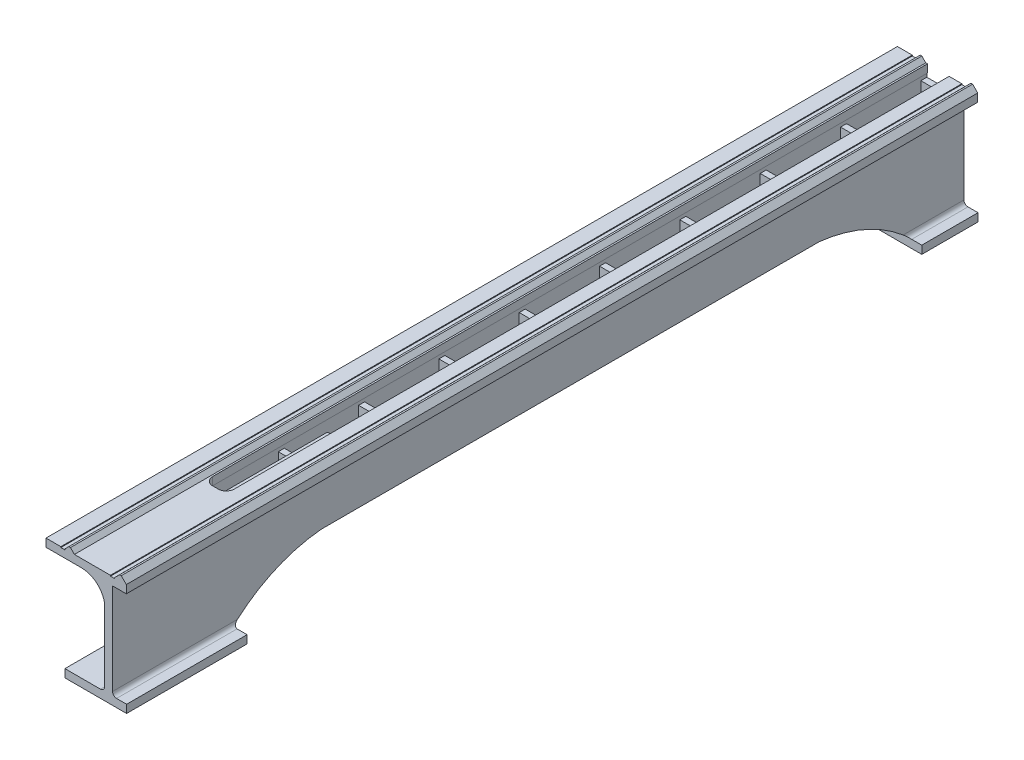
SolidWorks part; units mm, degrees
ref_plane "Front Plane" through (0, 0, 0) normal (0, 0, 1) x (1, 0, 0)
ref_plane "Top Plane" through (0, 0, 0) normal (0, 1, 0) x (1, 0, 0)
ref_plane "Right Plane" through (0, 0, 0) normal (1, 0, 0) x (0, 0, -1)
sketch "Sketch1" plane through (0, 0, 0) normal (0, 0, 1) x (1, 0, 0)
  line L0 (-31.5551, 31.2902) -> (-37.8538, 37.7187)
  line L2 (-131.555, 31.42) -> (-131.555, 21.42)
  line L4 (-31.5551, 31.2902) -> (-31.5551, 21.2902)
  line L5 (-37.8538, 37.7187) -> (-39.8538, 37.7187)
  line L6 (-39.8538, 37.7187) -> (-46.2824, 31.42)
  line L7 (-46.2824, 31.42) -> (-46.2824, 30.42)
  line L8 (-46.2824, 30.42) -> (-51.2824, 30.42)
  line L9 (-51.2824, 30.42) -> (-51.2824, 31.42)
  line L10 (-51.2824, 31.42) -> (-96.2063, 31.42)
  line L14 (-96.2063, 31.42) -> (-101.1053, 36.42)
  line L15 (-101.1053, 36.42) -> (-103.1053, 36.42)
  line L16 (-103.1053, 36.42) -> (-108.055, 31.4703)
  line L17 (-108.055, 31.4703) -> (-108.055, 30.42)
  line L18 (-108.055, 30.42) -> (-113.055, 30.42)
  line L19 (-113.055, 30.42) -> (-113.055, 31.42)
  line L20 (-113.055, 31.42) -> (-131.555, 31.42)
  line L21 (-131.555, 21.42) -> (-87.3496, 21.42)
  line L22 (-31.5551, 21.2902) -> (-48.7011, 21.2902)
  line L23 (-48.7011, 21.2902) -> (-48.7011, -92.58)
  line L24 (-43.7011, -97.58) -> (-31.1954, -97.58)
  line L25 (-31.1954, -97.58) -> (-31.1954, -107.58)
  line L26 (-31.1954, -107.58) -> (-108.01, -107.58)
  line L27 (-108.01, -107.58) -> (-108.01, -97.58)
  line L28 (-108.01, -97.58) -> (-63.7011, -97.58)
  line L29 (-58.7011, -92.58) -> (-58.7011, -1.9527)
  arc A0 (-87.3496, 21.42) -> (-58.7011, -1.9527) centre (-87.3496, -7.8239) cw
  arc A1 (-48.7011, -92.58) -> (-43.7011, -97.58) centre (-43.7011, -92.58) ccw
  arc A2 (-63.7011, -97.58) -> (-58.7011, -92.58) centre (-63.7011, -92.58) ccw
  point P30 (-48.7011, -97.58)
  dimension "D17" = 5
  dimension "D1" = 100
  dimension "D2" = 7
  dimension "D3" = 2
  dimension "D4" = 5
  dimension "D5" = 18.5
  dimension "D6" = 5
  dimension "D7" = 10
  dimension "D8" = 135
  dimension "D9" = 9
  dimension "D10" = 9
  dimension "D11" = 2
  dimension "D12" = 7
  dimension "D13" = 10
  dimension "D14" = 5
  dimension "D15" = 10
  dimension "D16" = 139
  dimension "D18" = 10
  dimension "D19" = 1
extrude "Boss-Extrude1" add sketch "Sketch1" along normal blind 1060
sketch "Sketch2" plane through (0, 20.7647, 0) normal (0, 1, 0) x (1, 0, 0)
  line L0 (-94.1707, -1200) -> (-94.1707, 0) construction
  line L1 (-84.1707, 100) -> (-77.1707, 100)
  line L2 (-94.1707, 90) -> (-94.1707, -890)
  line L3 (-84.1707, -900) -> (-77.1707, -900)
  line L4 (-67.1707, 90) -> (-67.1707, -890)
  line L5 (-67.1707, -1200) -> (-67.1707, 0) construction
  line L6 (-51.2824, 0) -> (-96.2063, 0) construction
  arc A0 (-94.1707, -890) -> (-84.1707, -900) centre (-84.1707, -890) ccw
  arc A1 (-77.1707, -900) -> (-67.1707, -890) centre (-77.1707, -890) ccw
  arc A2 (-77.1707, 100) -> (-67.1707, 90) centre (-77.1707, 90) cw
  arc A3 (-84.1707, 100) -> (-94.1707, 90) centre (-84.1707, 90) ccw
  point P12 (-67.1707, -900)
  point P15 (-67.1707, 100)
  point P18 (-94.1707, 100)
  dimension "D2" = 10
  dimension "D1" = 1000
  dimension "D3" = 100
extrude "Cut-Extrude1" cut sketch "Sketch2" along normal blind 800
sketch "Sketch3" plane through (0, 0, 1060) normal (0, 0, 1) x (1, 0, 0)
  line L1 (-57.7636, 8.0977) -> (-93.9675, 8.0977)
  line L2 (-57.7636, 8.0977) -> (-57.7636, 21.2819)
  line L3 (-57.7636, 21.2819) -> (-93.9675, 21.2819)
  line L4 (-93.9675, 8.0977) -> (-93.9675, 21.2819)
extrude "Cut-Extrude2" cut sketch "Sketch3" against normal blind 900 from offset 300 offset against normal yes
sketch "Sketch5" plane through (0, 0, 0) normal (0, 0, -1) x (-1, 0, 0)
  line L1 (105.3464, -97.4955) -> (94.9198, -97.4955)
  line L2 (105.3464, -97.4955) -> (105.3464, 27.7967)
  line L3 (105.3464, 27.7967) -> (94.9198, 27.7967)
  line L4 (94.9198, -97.4955) -> (94.9198, 27.7967)
extrude "Boss-Extrude2" add sketch "Sketch5" against normal blind 950
sketch "Sketch6" plane through (-105.3464, 0, 0) normal (-1, 0, 0) x (0, 0, 1)
  line L0 (0, -97.4955) -> (0, 21.42) construction
  line L1 (0, 16.5847) -> (7.4351, 16.5847)
  line L2 (0, 16.5847) -> (0, -47.4448)
  line L3 (0, -47.4448) -> (7.4351, -47.4448)
  line L4 (7.4351, 16.5847) -> (7.4351, -47.4448)
extrude "Boss-Extrude3" add sketch "Sketch6" against normal blind 50
pattern_linear "LPattern1" count 10 spacing 100 along (0, 0, 1) of "Boss-Extrude3"
sketch "Sketch4" plane through (-31.5551, 0, 0) normal (1, 0, 0) x (0, 0, -1)
  line L0 (-910, -97.58) -> (-910, -107.58)
  line L1 (-1060, -97.58) -> (0, -97.58) construction
  line L2 (-1060, -107.58) -> (0, -107.58) construction
  line L3 (-910, -107.58) -> (-910, -177.9566)
  line L4 (-910, -177.9566) -> (-70, -177.9566)
  line L5 (-70, -177.9566) -> (-70, -97.58)
  line L6 (-800, -47.58) -> (-180.0688, -47.58)
  line L7 (0, -92.58) -> (0, 21.2902) construction
  line L8 (-1060, -92.58) -> (-1060, 21.2902) construction
  arc A1 (-800, -47.58) -> (-910, -97.58) centre (-783.4011, -230.0975) ccw
  arc A2 (-180.0688, -47.58) -> (-70, -97.58) centre (-201.6096, -241.1508) cw
  point P17 (-795.844, -47.58)
  dimension "D1" = 60
  dimension "D2" = 70
  dimension "D3" = 150
  dimension "D4" = 110
  dimension "D5" = 110.0688
extrude "Cut-Extrude3" cut sketch "Sketch4" against normal blind 100 and the other way blind 10
